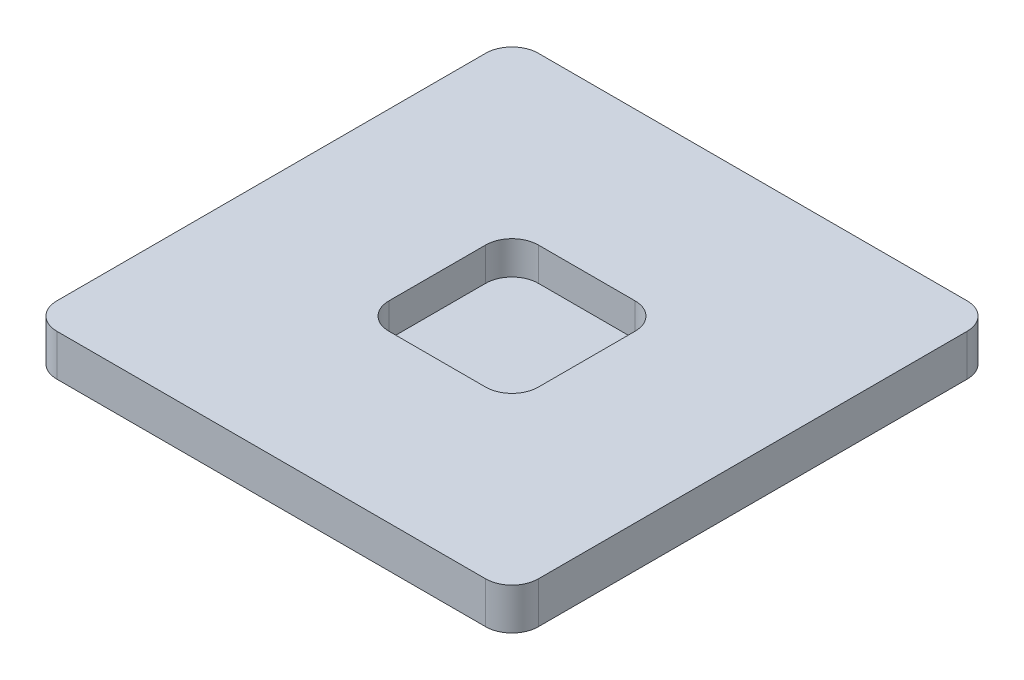
SolidWorks part; units mm, degrees
ref_plane "Front Plane" through (0, 0, 0) normal (0, 0, 1) x (1, 0, 0)
ref_plane "Top Plane" through (0, 0, 0) normal (0, 1, 0) x (1, 0, 0)
ref_plane "Right Plane" through (0, 0, 0) normal (1, 0, 0) x (0, 0, -1)
sketch "Sketch1" plane through (0, 0, 0) normal (0, 1, 0) x (1, 0, 0)
  line L1 (0, 0) -> (29, 0)
  line L2 (0, 0) -> (0, 29)
  line L3 (0, 29) -> (29, 29)
  line L4 (29, 0) -> (29, 29)
  dimension "D1" = 29
extrude "Boss-Extrude1" add sketch "Sketch1" along normal blind 7.5
sketch "Sketch8" plane through (0, 7.5, 0) normal (0, 1, 0) x (1, 0, 0)
  line L0 (14.5, 19) -> (14.5, 29) construction
  line L1 (10, 19) -> (19, 19)
  line L2 (10, 19) -> (10, 10)
  line L3 (10, 10) -> (19, 10)
  line L4 (19, 19) -> (19, 10)
  line L5 (29, 29) -> (0, 29) construction
  line L6 (19, 14.5) -> (29, 14.5) construction
  line L7 (29, 0) -> (29, 29) construction
  dimension "D1" = 9
extrude "Cut-Extrude3" cut sketch "Sketch8" against normal blind 2
sketch "Sketch9" plane through (0, 0, 0) normal (0, -1, 0) x (1, 0, 0)
  line L0 (14.5, -7) -> (14.5, 0) construction
  line L1 (7, -7) -> (22, -7)
  line L2 (7, -7) -> (7, -22)
  line L3 (7, -22) -> (22, -22)
  line L4 (0, 0) -> (0, -29)
  line L5 (0, -29) -> (29, -29)
  line L6 (29, -29) -> (29, 0)
  line L7 (29, 0) -> (0, 0)
  line L8 (0, 0) -> (0, -29)
  line L9 (0, -29) -> (29, -29)
  line L10 (29, -29) -> (29, 0)
  line L11 (29, 0) -> (0, 0)
  line L12 (22, -7) -> (22, -22)
  line L13 (22, -14.5) -> (29, -14.5) construction
  point P12 (3.8245, -4.0078)
  dimension "D2" = 15
  dimension "D1" = 0
extrude "Cut-Extrude4" cut sketch "Sketch9" against normal blind 5
sketch "Sketch10" plane through (0, 0, 0) normal (0, -1, 0) x (1, 0, 0)
  line L4 (22, -7) -> (7, -7) construction
  line L5 (12.75, -7) -> (16.25, -7)
  line L6 (12.75, -7) -> (12.75, -8.8254)
  line L7 (12.75, -22) -> (16.25, -22)
  line L8 (16.25, -7) -> (16.25, -8.8254)
  line L9 (7, -22) -> (22, -22) construction
  line L10 (7, -7) -> (7, -22) construction
  line L11 (7, -12.75) -> (8.8254, -12.75)
  line L12 (7, -12.75) -> (7, -16.25)
  line L13 (7, -16.25) -> (8.8254, -16.25)
  line L14 (22, -12.75) -> (22, -16.25)
  line L15 (22, -22) -> (22, -7) construction
  line L16 (20.1746, -12.75) -> (22, -12.75)
  line L17 (20.1746, -16.25) -> (22, -16.25)
  line L18 (16.25, -20.1746) -> (16.25, -22)
  line L19 (12.75, -20.1746) -> (12.75, -22)
  line L20 (7, -7) -> (7, -22) construction
  line L21 (12.75, -8.8254) -> (8.8254, -12.75)
  line L22 (8.8254, -16.25) -> (12.75, -20.1746)
  line L23 (16.25, -20.1746) -> (20.1746, -16.25)
  line L24 (20.1746, -12.75) -> (16.25, -8.8254)
  line L25 (14.5, -7.2522) -> (14.5, -7) construction
  line L26 (21.7478, -14.5) -> (22, -14.5) construction
  line L27 (14.5, -21.7478) -> (14.5, -22) construction
  line L28 (22, -22) -> (22, -7) construction
  point P18 (0, 0)
  point P20 (14.5, -10.397)
  point P27 (7, -14.5)
  point P28 (7, -14.5)
  point P32 (22, -14.5)
  point P35 (14.5, -9.6119)
  point P40 (0, 0)
  point P41 (0, 0)
  point P42 (0, 0)
  dimension "D1" = 3.5
  dimension "D2" = 10.5
  dimension "D3" = 45
  dimension "D4" = 45
extrude "Cut-Extrude5" cut sketch "Sketch10" against normal blind 2
fillet "Fillet1" radius 1.5875 16 edges at (16.25, 1, -8.8254) (20.1746, 1, -12.75) (20.1746, 1, -16.25) (16.25, 1, -20.1746) (12.75, 1, -20.1746) (8.8254, 1, -16.25) (8.8254, 1, -12.75) (12.75, 1, -8.8254) (0, 6.25, 0) (29, 6.25, 0) (29, 6.25, -29) (0, 6.25, -29) (10, 6.5, -10) (19, 6.5, -10) (19, 6.5, -19) (10, 6.5, -19)
